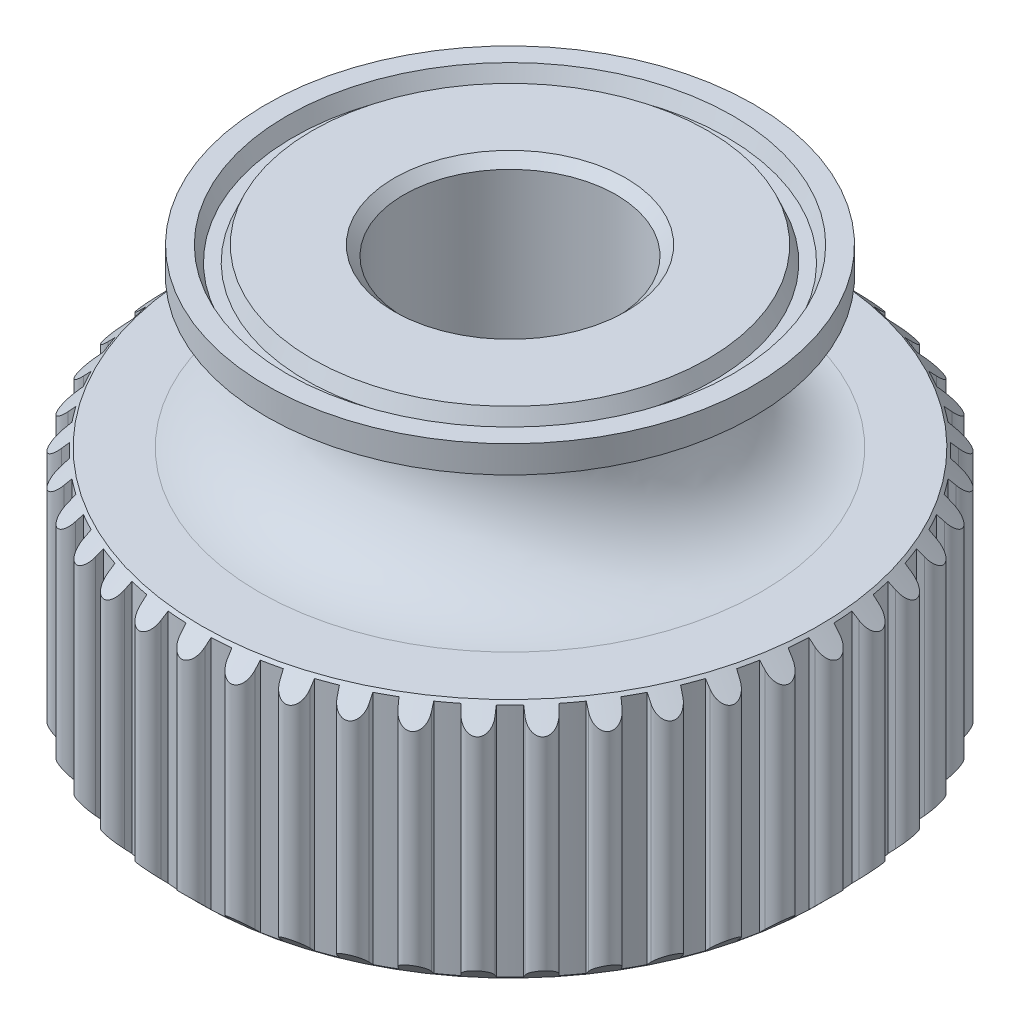
SolidWorks part; units mm, degrees
ref_plane "Front Plane" through (0, 0, 0) normal (0, 0, 1) x (1, 0, 0)
ref_plane "Top Plane" through (0, 0, 0) normal (0, 1, 0) x (1, 0, 0)
ref_plane "Right Plane" through (0, 0, 0) normal (1, 0, 0) x (0, 0, -1)
sketch "Sketch1" plane through (0, 0, 0) normal (0, 1, 0) x (1, 0, 0)
  circle A0 centre (0, 0) radius 25.3
  dimension "D1" = 50.6
extrude "Boss-Extrude1" add sketch "Sketch1" along normal blind 20
ref_plane "Plane1" through (0, 14.5, 0) normal (0, 1, 0) x (1, 0, 0)
sketch "Sketch2" plane through (0, 14.5, 0) normal (0, 1, 0) x (1, 0, 0)
  circle A0 centre (0, 0) radius 25.3
  circle A1 centre (0, 0) radius 25.3 construction
curve "Helix/Spiral1" pitch 5 height 17.5 radius 25.3 centre (0, 14.5, 0) axis (0, -1, 0) start towards (1, 0, 0)
ref_plane "Plane2" through (25.3, 14.5, 0) normal (0, -0.0314, 0.9995) x (1, 0, 0)
sketch "Sketch4" plane through (25.3, 14.5, 0) normal (0, -0.0314, 0.9995) x (1, 0, 0)
  line L0 (0, 1.6) -> (0.7, 1.6)
  line L1 (0.7, -1.6) -> (0.1, -1.6)
  line L4 (0, 0) -> (0.7, 0) construction
  line L5 (0, 1.6) -> (-0.5, 1.6)
  line L6 (-0.5, 1.6) -> (-0.5, -1.6)
  line L7 (-0.5, -1.6) -> (0.1, -1.6)
  arc A0 (0.7, 1.6) -> (0.7, -1.6) centre (0.7, 0) cw
  point P9 (2.3, 0)
  dimension "D1" = 1.6
  dimension "D2" = 3.2016
  dimension "D3" = 27.6
  dimension "D4" = 0.5
sweep "Sweep1" add profiles "Sketch4" path "Helix/Spiral1"
sketch "Sketch7" plane through (0, 14.5, 0) normal (0, 1, 0) x (1, 0, 0)
  line L0 (25.3, 0) -> (25.3, 0.1)
  arc A0 (25.3, 0.1) -> (22.4349, 2.1614) centre (23.1259, 0.1) ccw
  dimension "D1" = 0.1
sweep "Sweep3" add profiles "Sketch4<2>" path "Sketch7"
sketch "Sketch4<2>" plane through (25.3, 14.5, 0) normal (0, -0.0314, 0.9995) x (1, 0, 0) same geometry as "Sketch4"
ref_plane "Plane3" [suppressed] through (0, 2, 0) normal (0, 1, 0) x (1, 0, 0)
sketch "Sketch9" [suppressed] plane through (0, 2, 0) normal (0, 1, 0) x (1, 0, 0)
  line L0 (-25.1, 0) -> (-25.1, 0.1)
  arc A0 (-25.1, 0.1) -> (-23.8332, 1.5151) centre (-23.6762, 0.1) cw
  dimension "D1" = 0.1
sketch "Sketch11" plane through (0, 0, 0) normal (0, -1, 0) x (1, 0, 0)
  circle A0 centre (0, 0) radius 32.3608
extrude "Cut-Extrude1" [suppressed] cut sketch "Sketch11" along normal blind 17
sketch "Sketch10" plane through (0, 0, 0) normal (0, 1, 0) x (1, 0, 0)
  arc A2 (-28.3266, 15.5208) -> (6.045, -31.7293) centre (0, 0) ccw
  circle A3 centre (0, 0) radius 32.3
  dimension "D1" = 7
extrude "Boss-Extrude2" add sketch "Sketch10" along normal offset from surface (25 mm away) 5 separate body up to face at (0, 20, 25.3) offset beyond the face yes
combine bodies "Combine1" operation type subtract main body 105 bodies to subtract 103
sketch "Sketch12" plane through (0, 0, 0) normal (0, -1, 0) x (1, 0, 0)
  circle A0 centre (0, 0) radius 27.5
  dimension "D1" = 55
extrude "Cut-Extrude2" cut sketch "Sketch12" against normal blind 2
sketch "Sketch13" plane through (0, 2, 0) normal (0, -1, 0) x (1, 0, 0)
  line L0 (11.0663, 23.5274) -> (12.5874, 21.9465)
  line L1 (12.5874, 21.9465) -> (8.0116, 20.7982)
  line L2 (8.0116, 20.7982) -> (5.8064, 24.0491)
  line L3 (5.8064, 24.0491) -> (11.0663, 23.5274)
  arc A0 (10.7696, -22.8934) -> (10.7696, 22.8934) centre (0, 0) ccw construction
extrude "Cut-Extrude3" cut sketch "Sketch13" against normal blind 1
sketch "Sketch15" plane through (0, 0, 0) normal (0, 0, 1) x (1, 0, 0)
  line L0 (-16, 25) -> (-16, 37)
  line L1 (-16, 37) -> (-25.25, 40.3667)
  line L2 (-25.25, 40.3667) -> (-25.25, 43.1734)
  line L3 (-25.25, 43.1734) -> (-23.1371, 43.1734)
  line L4 (-11, 43.1734) -> (-11, 25)
  line L5 (-11, 25) -> (-16, 25)
  line L6 (32.3, 25) -> (-32.3, 25) construction
  line L7 (0, 0) -> (0, 60.588) construction
  line L8 (-20.5001, 43.1734) -> (-21.1686, 41.5986)
  line L9 (-21.1686, 41.5986) -> (-22.4686, 41.5986)
  line L10 (-22.4686, 41.5986) -> (-23.1371, 43.1734)
  line L11 (-21.8186, 41.5986) -> (-21.8186, 43.1734) construction
  line L12 (-20.5001, 43.1734) -> (-11, 43.1734)
  arc A0 (-20.6686, 43.1734) -> (-22.9686, 43.1734) centre (-21.8186, 43.1734) cw construction
  dimension "D11" = 1.15
  dimension "D1" = 50.5
  dimension "D2" = 2.8067
  dimension "D3" = 20
  dimension "D4" = 22
  dimension "D5" = 12
  dimension "D6" = 5
  dimension "D7" = 46
  dimension "D8" = 21.8186
  dimension "D9" = 1.5748
  dimension "D10" = 1.3
revolve "Revolve1" add sketch "Sketch15" angle 360 about L7
sketch "Sketch16" plane through (0, 25, 0) normal (0, 1, 0) x (1, 0, 0)
  circle A1 centre (0, 0) radius 11
  circle A2 centre (0, 0) radius 11
  dimension "D1" = 0
extrude "Cut-Extrude4" cut sketch "Sketch16" against normal through all
fillet "Fillet2" radius 1.143 1 edges at (0, 37, -16)
fillet "Fillet3" radius 10 1 edges at (0, 25, -16)
chamfer "Chamfer2" distance 1 angle 45 2 edges at (0, 20, 11) (0, 43.1734, -11)
sketch "Sketch17" plane through (0, 0, 0) normal (0, 1, 0) x (1, 0, 0)
  line L0 (1.3025, 32.2737) -> (1.25, 32.8737)
  line L1 (-1.25, 32.8737) -> (-1.3025, 32.2737)
  line L2 (0, 0) -> (0, 32.7644) construction
  circle A0 centre (0, 0) radius 32.3 construction
  arc A1 (1.25, 32.8737) -> (-1.25, 32.8737) centre (0, 32.7644) ccw
  arc A2 (1.3025, 32.2737) -> (-1.3025, 32.2737) centre (0, 0) ccw
  point P6 (0, 32.3)
  point P9 (0, 31.5096)
  dimension "D1" = 5
  dimension "D2" = 0.6
  dimension "D3" = 2.5
extrude "Boss-Extrude3" add sketch "Sketch17" along normal up to surface (25 mm away) up to face at (0, 25, 26)
pattern_circular "CirPattern1" count 44 over 360 about axis through (0, 25, 0) along (0, 1, 0) of "Boss-Extrude3"
ref_axis "Axis1" through (0, 45.4444, 0) along (0, -1, 0)
sketch "Sketch18" plane through (0, 0, 0) normal (1, 0, 0) x (0, 0, -1)
  line L0 (-34.0191, 23) -> (-32.0191, 25)
  line L1 (-32.0191, 25) -> (-34.0191, 25)
  line L2 (-34.0191, 25) -> (-34.0191, 23)
  dimension "D1" = 2
revolve "Cut-Revolve1" cut sketch "Sketch18" angle 360 about axis through (0, 45.4444, 0) along (0, -1, 0)
ref_plane "Plane4" through (0, 12.5, 0) normal (0, 1, 0) x (1, 0, 0)
mirror "Mirror1" about plane through (0, 12.5, 0) normal (0, 1, 0) of "Cut-Revolve1"
